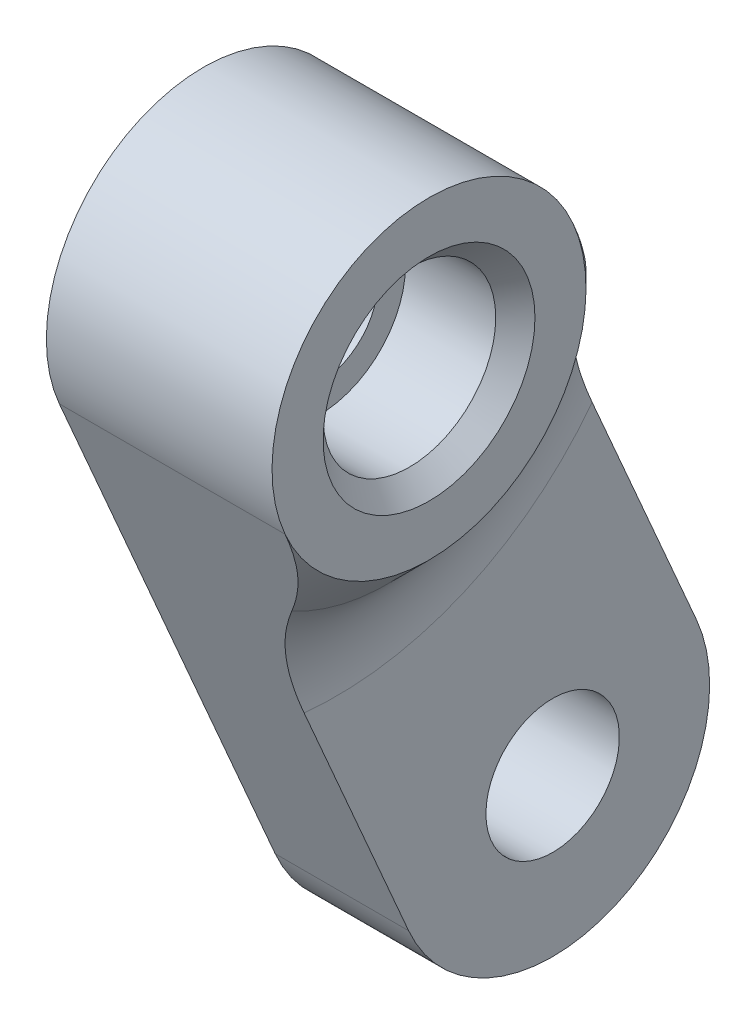
SolidWorks part; units mm, degrees
ref_plane "Front Plane" through (0, 0, 0) normal (0, 0, 1) x (1, 0, 0)
ref_plane "Top Plane" through (0, 0, 0) normal (0, 1, 0) x (1, 0, 0)
ref_plane "Right Plane" through (0, 0, 0) normal (1, 0, 0) x (0, 0, -1)
ref_plane "Plane1" through (-31.5964, 0, 0) normal (1, 0, 0) x (0, 0, -1)
sketch "Sketch1" plane through (-31.5964, 0, 0) normal (1, 0, 0) x (0, 0, -1)
  line L0 (30.8305, -54.3328) -> (36.3305, -67.0097)
  line L1 (43.6695, -63.8256) -> (38.1695, -51.1487)
  arc A0 (38.1695, -51.1487) -> (30.8305, -54.3328) centre (34.5, -52.7408) ccw
  arc A1 (36.3305, -67.0097) -> (43.6695, -63.8256) centre (40, -65.4176) ccw
extrude "Boss-Extrude1" add sketch "Sketch1" against normal blind 5.75
sketch "Sketch2" plane through (-31.5964, 0, 0) normal (1, 0, 0) x (0, 0, -1)
  line L0 (32.7934, -58.8572) -> (36.3305, -67.0097)
  line L1 (43.6695, -63.8256) -> (40.1324, -55.673)
  arc A0 (40.1324, -55.673) -> (32.7934, -58.8572) centre (34.5, -52.7408) cw
  arc A1 (36.3305, -67.0097) -> (43.6695, -63.8256) centre (40, -65.4176) ccw
extrude "Cut-Extrude1" cut sketch "Sketch2" against normal blind 2.35
draft "Draft1" type of draft neutral plane draft angle 45 faces to draft 1 face at (-32.7714, -57.9156, -36.7452) neutral plane through (-33.9464, -52.7408, -34.5) neutral plane normal (1, 0, 0) parameters "D1"=45
hole_wizard "Hole1" positions "Sketch4" profile "Sketch3" legacy end condition through all
sketch "Sketch4" plane through (-37.3464, 0, 0) normal (-1, 0, 0) x (0, 0, 1)
  point P0 (-40, -65.4176)
sketch "Sketch3" plane through (-37.3464, -65.4176, -40) normal (0, 1, 0) x (0, 0, 1)
  line L0 (0, 0) -> (0, 5.75)
  line L1 (0, 5.75) -> (1.7, 5.75)
  line L2 (1.7, 5.75) -> (1.7, 0)
  line L3 (1.7, 0) -> (0, 0)
  line L4 (0, 110) -> (0, -10) construction
  dimension "Diameter" = 3.4
  dimension "Depth" = 5.75
hole_wizard "Hole2" positions "Sketch6" profile "Sketch5" legacy
sketch "Sketch6" plane through (-31.5964, 0, 0) normal (1, 0, 0) x (0, 0, -1)
  point P0 (34.5, -52.7408)
sketch "Sketch5" plane through (-31.5964, -52.7408, -34.5) normal (0, 1, 0) x (0, 0, -1)
  line L0 (0, 0) -> (0, 5.75)
  line L1 (0, 5.75) -> (1.5, 5.75)
  line L2 (1.5, 5.75) -> (1.5, 2.8)
  line L3 (1.5, 2.8) -> (2.2, 2.8)
  line L4 (2.2, 2.8) -> (2.2, 0)
  line L5 (2.2, 0) -> (0, 0)
  line L6 (0, 110) -> (0, -10) construction
  dimension "Diameter" = 3
  dimension "Depth" = 5.75
  dimension "C-Bore Diameter" = 4.4
  dimension "C-Bore Depth" = 2.8
chamfer "Chamfer1" distance 0.5 angle 45 1 edges at (-31.5964, -52.7408, -36.7)
fillet "Fillet1" radius 4.4 1 edges at (-33.9464, -58.5661, -37.0274) tangent propagation no
